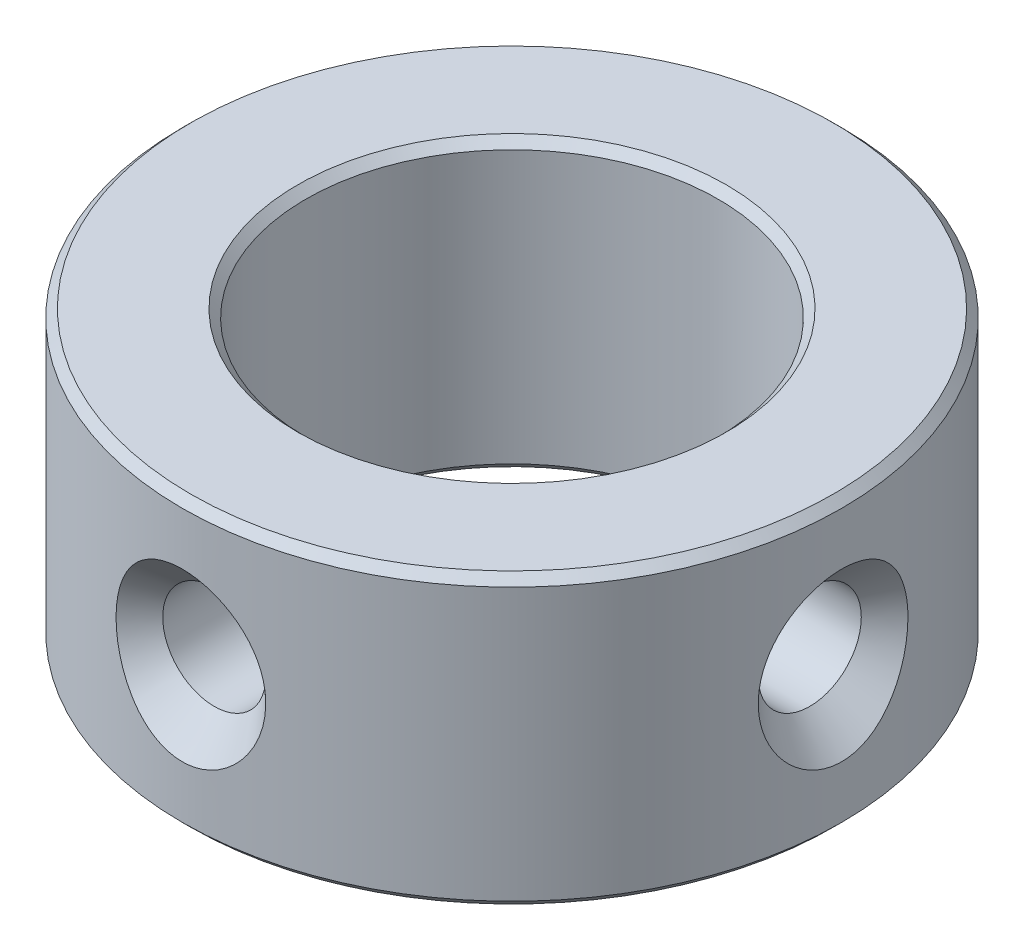
SolidWorks part; units mm, degrees
material "6061-T6 (SS)"
ref_plane "Front Plane" through (0, 0, 0) normal (0, 0, 1) x (1, 0, 0)
ref_plane "Top Plane" through (0, 0, 0) normal (0, 1, 0) x (1, 0, 0)
ref_plane "Right Plane" through (0, 0, 0) normal (1, 0, 0) x (0, 0, -1)
sketch "Profile Sketch" plane through (0, 0, 0) normal (0, 1, 0) x (1, 0, 0)
  circle A0 centre (0, 0) radius 5
  circle A1 centre (0, 0) radius 8
  dimension "InnerDia" = 10
  dimension "RefOuterDia" = 16
  dimension "DiaControl" = 3
extrude "Profile" add sketch "Profile Sketch" along normal mid plane 7
ref_plane "SetScrewPlane" through (0, 0, 8) normal (0, 0, 1) x (1, 0, 0)
hole_wizard " Tapped Hole1" positions "Sketch1" profile "Sketch2" tap size "M3x0.5" standard "ANSI Metric" end condition up to next
sketch "Sketch1" plane through (0, 0, 8) normal (0, 0, 1) x (1, 0, 0)
  point P0 (0, 0)
sketch "Sketch2" plane through (0, 0, 8) normal (1, 0, 0) x (0, -1, 0)
  line L0 (0, 0) -> (0, 3)
  line L1 (0, 3) -> (1.25, 3)
  line L2 (1.25, 3) -> (1.25, 0.775)
  line L3 (1.25, 0.775) -> (2.025, 0)
  line L5 (2.025, 0) -> (0, 0)
  line L6 (-1.25, 0.775) -> (-2.025, 0) construction
  line L11 (0, -6.35) -> (0, 107.95) construction
  dimension "Thru Tap Drill Dia." = 2.5
  dimension "Thru Tap Drill Depth" = 3
  dimension "Near C'Sink Dia." = 4.05
  dimension "Near C'Sink Angle" = 90
cosmetic thread "Hole Thread1" parameters "D2"=3
pattern_circular "Set Screw Circular Pattern" count 2 every 90 about axis through (0, 3.5, 0) along (0, -1, 0) of " Tapped Hole1" reverse direction yes
chamfer "Outer Chamfer" distance 0.2 angle 45 2 edges at (0, 3.5, 8) (0, -3.5, 8)
chamfer "Inner Chamfer" distance 0.2 angle 45 2 edges at (0, 3.5, 5) (0, -3.5, 5)
